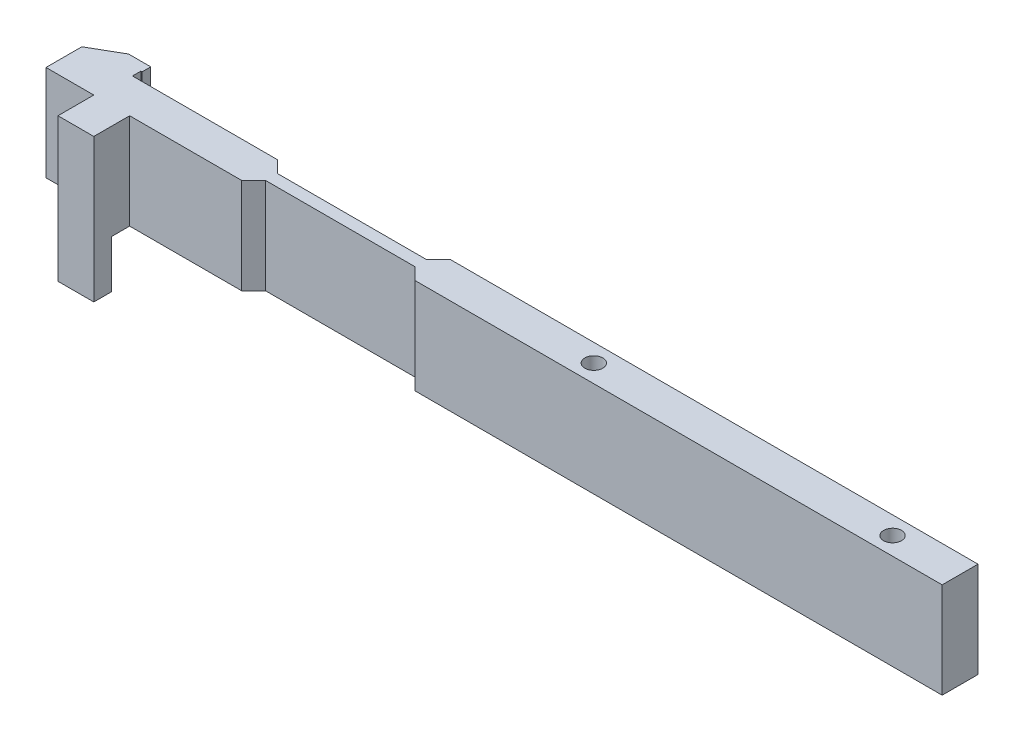
SolidWorks part; units mm, degrees
ref_plane "Спереди" through (0, 0, 0) normal (0, 0, 1) x (1, 0, 0)
ref_plane "Сверху" through (0, 0, 0) normal (0, 1, 0) x (1, 0, 0)
ref_plane "Справа" through (0, 0, 0) normal (1, 0, 0) x (0, 0, -1)
sketch "Эскиз1" plane through (0, 0, 0) normal (0, 1, 0) x (1, 0, 0)
  line L0 (0, 0) -> (-71.5259, 0)
  line L1 (-71.5259, 0) -> (-71.5259, 1.3965)
  line L2 (-71.5259, 1.3965) -> (-71.3259, 1.3965)
  line L3 (-71.3259, 1.3965) -> (-71.3259, 2.8586)
  line L4 (-71.3259, 2.8586) -> (-75.0357, 2.8586)
  line L5 (-75.0357, 2.8586) -> (-80, -0.0075)
  line L6 (-80, -0.0075) -> (-80, -6)
  line L7 (-80, -6) -> (70, -6)
  line L8 (70, -6) -> (70, 0)
  line L9 (70, 0) -> (0, 0)
  dimension "D1" = 150
  dimension "D2" = 30
  dimension "D3" = 0.2
  dimension "D4" = 6
  dimension "D5" = 70
extrude "Бобышка-Вытянуть1" add sketch "Эскиз1" along normal blind 16
sketch "Эскиз3" plane through (0, 16, 0) normal (0, 1, 0) x (1, 0, 0)
  line L0 (70, -3.0038) -> (-80, -3.0038) construction
  line L2 (-80, -0.0075) -> (-80, -6) construction
  line L3 (-47.2432, 0) -> (-45.2394, -2.0038)
  line L4 (70, 0) -> (-71.5259, 0) construction
  line L5 (-45.2394, -2.0038) -> (-20.2704, -2.0038)
  line L6 (-20.2704, -2.0038) -> (-18.2666, 0)
  line L7 (-47.2432, 0) -> (-18.2666, 0)
  line L8 (-47.2432, -6.0075) -> (-18.2666, -6.0075)
  line L9 (-20.2704, -4.0038) -> (-18.2666, -6.0075)
  line L10 (-45.2394, -4.0038) -> (-20.2704, -4.0038)
  line L11 (-47.2432, -6.0075) -> (-45.2394, -4.0038)
  circle A0 centre (8.6991, -3.0038) radius 1.5
  circle A1 centre (58.6991, -3.0038) radius 1.5
  dimension "D1" = 3
  dimension "D2" = 45
  dimension "D3" = 2
  dimension "D4" = 2
extrude "Вырез-Вытянуть1" cut sketch "Эскиз3" against normal through all
sketch "Эскиз4" plane through (0, 0, 0) normal (0, -1, 0) x (1, 0, 0)
  line L0 (-80, 6) -> (-47.2357, 6) construction
  line L1 (-80, 6) -> (-47.2357, 6) construction
  line L3 (-72, 12) -> (-66, 12)
  line L4 (-72, 12) -> (-72, 6)
  line L5 (-72, 6) -> (-66, 6)
  line L6 (-66, 12) -> (-66, 6)
  line L7 (-72, 12) -> (-66, 6) construction
  line L8 (-72, 6) -> (-66, 12) construction
  point P2 (-69, 9)
  dimension "D1" = 6
  dimension "D2" = 8
extrude "Бобышка-Вытянуть2" add sketch "Эскиз4" against normal up to surface (16 mm away) up to face at (58.6991, 16, 4.5038)
sketch "Эскиз5" plane through (0, 16, 0) normal (0, 1, 0) x (1, 0, 0)
  line L0 (-72, -12) -> (-72, -6)
  line L3 (-66, -12) -> (-66, -6) construction
  line L4 (-66, -9) -> (-66, -12)
  line L5 (-66, -12) -> (-72, -12)
  line L6 (-69, -12) -> (-69, -6) construction
  line L9 (-72, -6) -> (-66, -9)
extrude "Бобышка-Вытянуть3" [suppressed] add sketch "Эскиз5" along normal blind 8
extrude "Бобышка-Вытянуть4" add sketch "Эскиз5<2>" against normal blind 8 from surface starting at face at (58.6991, 0, 4.5038)
sketch "Эскиз5<2>" plane through (0, 16, 0) normal (0, 1, 0) x (1, 0, 0) same geometry as "Эскиз5"
sketch "Эскиз6" [suppressed] plane through (0, 0, 0) normal (0, -1, 0) x (1, 0, 0)
  line L3 (-80, 6) -> (-80, 0.0075)
extrude "Вырез-Вытянуть2" [suppressed] cut sketch "Эскиз6" against normal through all
sketch "Эскиз7" plane through (0, 0, 0) normal (0, -1, 0) x (-1, 0, 0)
  line L1 (72, -12) -> (66, -12)
  line L2 (66, -12) -> (66, -6)
extrude "Вырез-Вытянуть3" [suppressed] cut sketch "Эскиз7" against normal through all
